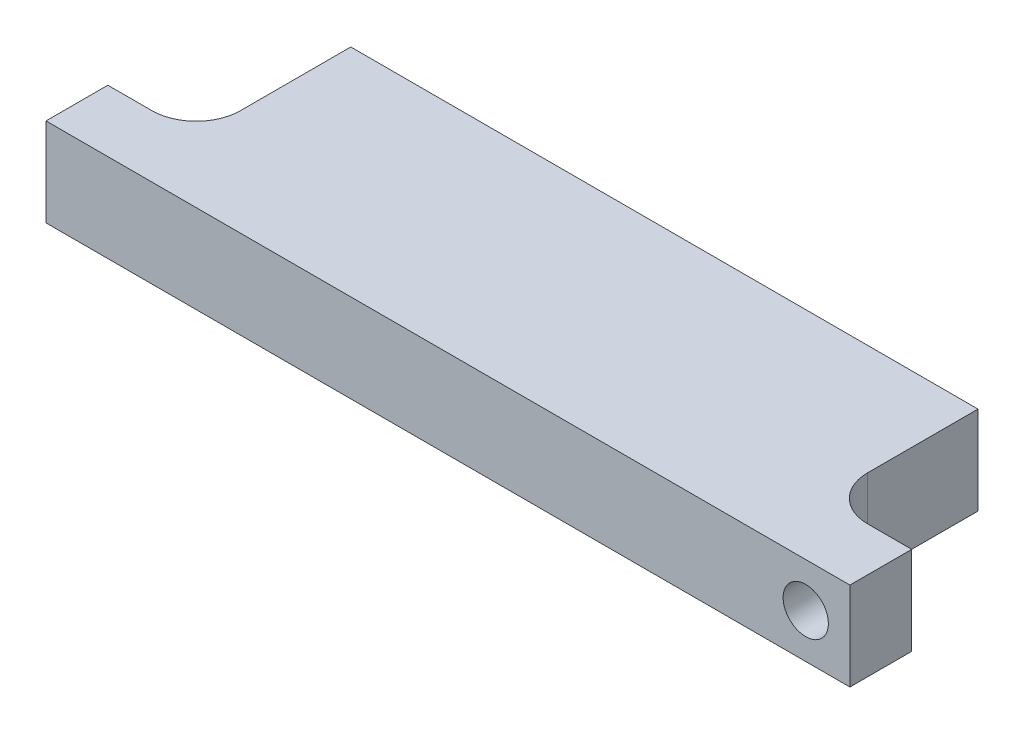
SolidWorks part; units mm, degrees
material "6061 Alloy"
ref_plane "Front Plane" through (0, 0, 0) normal (0, 0, 1) x (1, 0, 0)
ref_plane "Top Plane" through (0, 0, 0) normal (0, 1, 0) x (1, 0, 0)
ref_plane "Right Plane" through (0, 0, 0) normal (1, 0, 0) x (0, 0, -1)
ref_plane "Plane1" through (0, 4, 0) normal (0, 1, 0) x (1, 0, 0)
sketch "Sketch1" plane through (0, 4, 0) normal (0, 1, 0) x (1, 0, 0)
  line L0 (18.2, 0) -> (-18.2, 0)
  line L1 (-18.2, 0) -> (-18.2, -9.8)
  line L2 (-18.2, -9.8) -> (18.2, -9.8)
  line L3 (18.2, -9.8) -> (18.2, 0)
extrude "Boss-Extrude1" add sketch "Sketch1" against normal blind 4
sketch "Sketch2" plane through (0, 0, 0) normal (0, -1, 0) x (1, 0, 0)
  line L0 (-14.2, 7) -> (-18.2, 7)
  line L1 (-18.2, 7) -> (-18.2, 0)
  line L2 (-18.2, 0) -> (-14.2, 0)
  line L3 (-14.2, 0) -> (-14.2, 7)
extrude "Cut-Extrude1" cut sketch "Sketch2" against normal through all
sketch "Sketch3" plane through (0, 0, 0) normal (0, -1, 0) x (1, 0, 0)
  line L0 (18.2, 7) -> (14.2, 7)
  line L1 (14.2, 7) -> (14.2, 0)
  line L2 (14.2, 0) -> (18.2, 0)
  line L3 (18.2, 0) -> (18.2, 7)
extrude "Cut-Extrude2" cut sketch "Sketch3" against normal through all
hole_wizard "M2.5x0.45 Tapped Hole1" positions "Sketch5" profile "Sketch4" tap size "M2.5x0.45" standard "ANSI Metric"
sketch "Sketch5" plane through (0, 0, 0) normal (0, 0, -1) x (-1, 0, 0)
  point P0 (10, 2)
  point P1 (-10, 2)
sketch "Sketch4" plane through (-10, 2, 0) normal (1, 0, 0) x (0, 1, 0)
  line L0 (0, 0) -> (0, 6.9659)
  line L1 (0, 6.9659) -> (1.025, 6.35)
  line L2 (1.025, 6.35) -> (1.025, 0)
  line L5 (1.025, 0) -> (0, 0)
  line L10 (0, 6.9659) -> (-1.025, 6.35) construction
  line L11 (0, -6.35) -> (0, 107.95) construction
  dimension "Tap Drill Dia." = 2.05
  dimension "Tap Drill Depth" = 6.35
  dimension "Drill Angle" = 118
hole_wizard "M2.5x0.45 Tapped Hole2" positions "Sketch7" profile "Sketch6" tap size "M2.5x0.45" standard "ANSI Metric" end condition up to next
sketch "Sketch7" plane through (0, 0, 9.8) normal (0, 0, 1) x (1, 0, 0)
  point P0 (16.2, 2)
sketch "Sketch6" plane through (16.2, 2, 9.8) normal (1, 0, 0) x (0, -1, 0)
  line L0 (0, 0) -> (0, 2.8)
  line L1 (0, 2.8) -> (1.025, 2.8)
  line L2 (1.025, 2.8) -> (1.025, 0)
  line L5 (1.025, 0) -> (0, 0)
  line L11 (0, -6.35) -> (0, 107.95) construction
  dimension "Thread Major Dia." = 2.05
  dimension "Thru Tap Drill Depth" = 2.8
fillet "Fillet1" radius 2 2 edges at (14.2, 2, 7) (-14.2, 2, 7)
